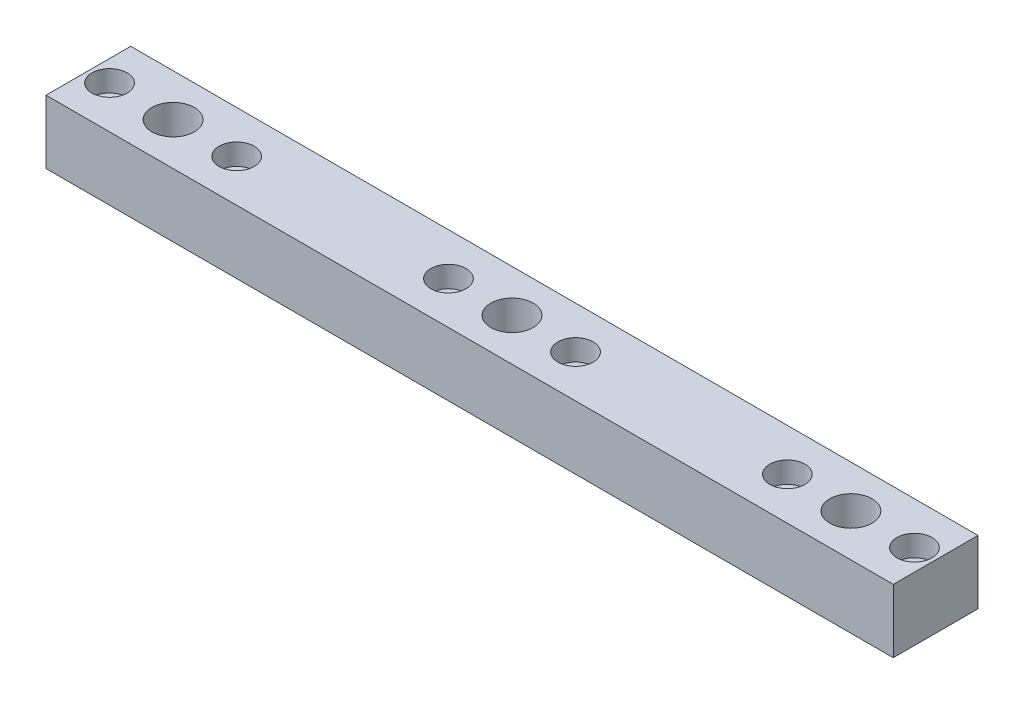
SolidWorks part; units mm, degrees
ref_plane "Front Plane" through (0, 0, 0) normal (0, 0, 1) x (1, 0, 0)
ref_plane "Top Plane" through (0, 0, 0) normal (0, 1, 0) x (1, 0, 0)
ref_plane "Right Plane" through (0, 0, 0) normal (1, 0, 0) x (0, 0, -1)
sketch "Sketch1" plane through (0, 0, 0) normal (0, 1, 0) x (1, 0, 0)
  line L1 (0, 0) -> (200, 0)
  line L2 (0, 0) -> (0, 20)
  line L3 (0, 20) -> (200, 20)
  line L4 (200, 0) -> (200, 20)
  circle A0 centre (20, 10) radius 5
  circle A1 centre (35, 10) radius 2.5
  circle A2 centre (5, 10) radius 2.5
  circle A3 centre (180, 10) radius 5
  circle A4 centre (195, 10) radius 2.5
  circle A5 centre (165, 10) radius 2.5
  circle A6 centre (100, 10) radius 5
  circle A7 centre (115, 10) radius 2.5
  circle A8 centre (85, 10) radius 2.5
  dimension "D1" = 200
  dimension "D2" = 20
extrude "Boss-Extrude1" add sketch "Sketch1" along normal blind 15
sketch "Sketch2" plane through (0, 15, 0) normal (0, 1, 0) x (1, 0, 0)
  circle A0 centre (5, 10) radius 4.15
  circle A1 centre (35, 10) radius 4.15
  circle A2 centre (85, 10) radius 4.15
  circle A3 centre (115, 10) radius 4.15
  circle A4 centre (165, 10) radius 4.15
  circle A5 centre (195, 10) radius 4.15
extrude "Cut-Extrude1" cut sketch "Sketch2" against normal blind 5
